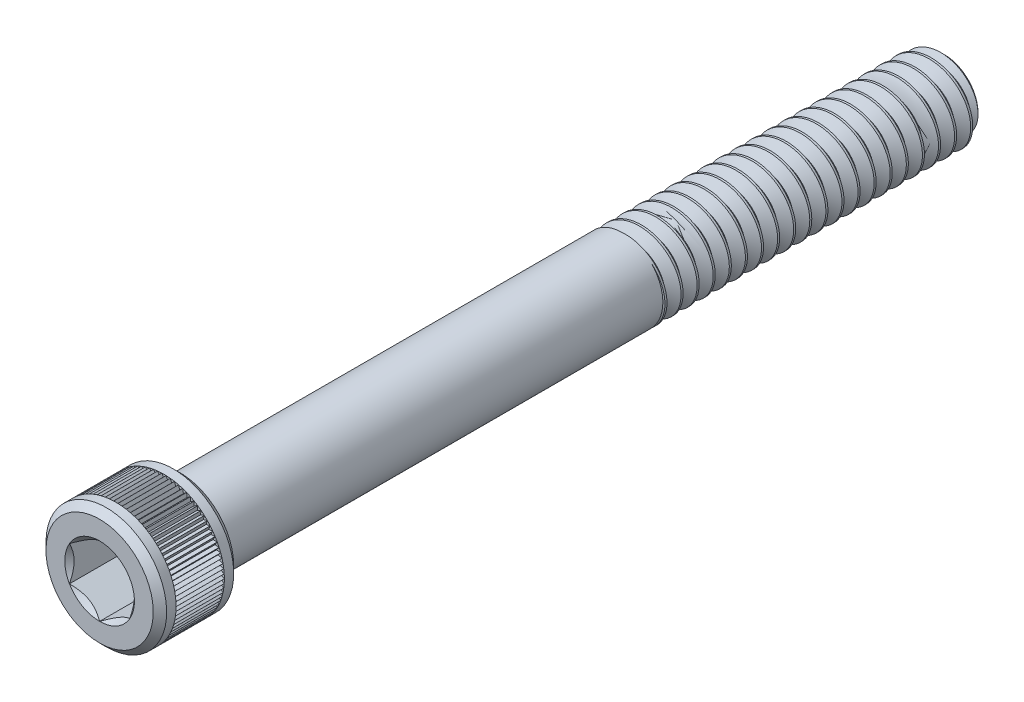
SolidWorks part; units mm, degrees
ref_plane "Front Plane" through (0, 0, 0) normal (0, 0, 1) x (1, 0, 0)
ref_plane "Top Plane" through (0, 0, 0) normal (0, 1, 0) x (1, 0, 0)
ref_plane "Right Plane" through (0, 0, 0) normal (1, 0, 0) x (0, 0, -1)
sketch "Sketch1" plane through (0, 0, 0) normal (1, 0, 0) x (0, 0, -1)
  line L0 (-34.925, 0) -> (25.4, 0) construction
  line L1 (-34.925, 4.7625) -> (-34.925, -4.7625) construction
  line L2 (25.4, 3.175) -> (25.4, -3.175) construction
  line L3 (25.4, 3.175) -> (26.67, 3.175) construction
  line L4 (-34.925, 4.7625) -> (-41.275, 4.7625) construction
  line L5 (-41.275, -2.3812) -> (-41.275, 2.3812) construction
  point P5 (0, 3.175)
  point P6 (22.225, -3.175)
  point P9 (25.4, 0)
  point P14 (-41.275, 0)
  point P15 (-22.225, 0)
  point P16 (-12.7, 0)
  point P17 (-40.005, 4.7625)
  point P18 (-36.195, 4.7625)
  dimension "Pitch" = 1.27
  dimension "Thread OD" = 6.35
  dimension "Minimum Thread Length" = 25.4
  dimension "Head Diameter" = 9.525
  dimension "Head Height" = 6.35
  dimension "Length" = 60.325
  dimension "Drive Size" = 4.7625
  dimension "D1" = 3.175
  dimension "D2" = 12.7
  dimension "D3" = 12.7
  dimension "D4" = 1.27
  dimension "D5" = 1.27
sketch "Sketch12" plane through (0, 0, 0) normal (0, 0, 1) x (1, 0, 0)
  line L0 (-0.1663, 4.7625) -> (0.1663, 4.7625)
  line L1 (0.1663, 4.7625) -> (0, 4.4744)
  line L2 (0, 4.4744) -> (-0.1663, 4.7625)
  line L3 (-0.1663, 4.7625) -> (0, 0) construction
  line L4 (0, 0) -> (0.1663, 4.7625) construction
  dimension "Knurl Angle" = 4
sketch "Sketch2" plane through (0, 0, 0) normal (1, 0, 0) x (0, 0, -1)
  line L0 (-41.275, 0) -> (25.4, 0)
  line L1 (-40.7458, 4.7625) -> (-35.4542, 4.7625)
  line L2 (-41.275, 4.2333) -> (-41.275, 0)
  line L4 (-34.925, 4.2333) -> (-34.925, 3.175)
  line L5 (25.4, 0) -> (25.4, 2.6458)
  line L6 (24.8708, 3.175) -> (-34.925, 3.175)
  line L7 (-34.925, 4.2333) -> (-35.4542, 4.7625)
  line L8 (-41.275, 4.2333) -> (-40.7458, 4.7625)
  line L9 (24.8708, 3.175) -> (25.4, 2.6458)
  line L10 (-34.925, 4.7625) -> (-41.275, 4.7625) construction
  line L11 (-34.925, 4.7625) -> (-34.925, -4.7625) construction
  point P0 (-38.1, 4.7625)
  dimension "D1" = 45
  dimension "D2" = 0.5292
revolve "Revolve1" add sketch "Sketch2" angle 360 about L0
sketch "Sketch3" plane through (0, 0, 41.275) normal (0, 0, 1) x (1, 0, 0)
  line L0 (-2.3813, 0) -> (2.3812, 0) construction
  line L1 (0, 2.7496) -> (-2.3813, 1.3748)
  line L2 (-2.3813, 1.3748) -> (-2.3813, -1.3748)
  line L3 (-2.3813, -1.3748) -> (0, -2.7496)
  line L4 (0, -2.7496) -> (2.3813, -1.3748)
  line L5 (2.3813, -1.3748) -> (2.3813, 1.3748)
  line L6 (2.3813, 1.3748) -> (0, 2.7496)
  line L7 (0, -2.3812) -> (0, 2.3812) construction
  circle A0 centre (0, 0) radius 2.3813 construction
extrude "Cut-Extrude1" cut sketch "Sketch3" against normal blind 4.7625
sketch "Sketch4" plane through (0, 0, 41.275) normal (0, 0, 1) x (1, 0, 0)
  circle A0 centre (0, 0) radius 2.7496
extrude "Cut-Extrude2" cut sketch "Sketch4" against normal through all draft 45
split "Split1" trim tools "Front Plane" bodies to split 106 resulting bodies 107 108
sketch "Sketch6" plane through (0, 0, -25.4) normal (0, 0, -1) x (-1, 0, 0)
  line L0 (0, -2.3812) -> (0, 2.3812) construction
  circle A0 centre (0, 0) radius 3.175
sketch "Sketch7" plane through (0, 0, 0) normal (1, 0, 0) x (0, 0, -1)
  line L0 (25.4, 3.175) -> (26.5113, 3.175) construction
  line L1 (26.5113, 3.175) -> (25.9556, 2.2126) construction
  line L2 (25.9556, 2.2126) -> (25.4, 3.175) construction
  line L3 (25.4, 3.175) -> (25.3206, 3.3125) construction
  line L4 (25.3206, 3.3125) -> (26.5906, 3.3125) construction
  line L5 (26.5906, 3.3125) -> (26.5113, 3.175) construction
  line L6 (25.8763, 2.3501) -> (26.035, 2.3501) construction
  line L7 (25.9556, 3.175) -> (25.9556, 3.3125) construction
  line L8 (25.9556, 2.3501) -> (25.9556, 2.2126) construction
  line L9 (25.4, 3.175) -> (26.67, 3.175) construction
  dimension "D1" = 0.1588
curve "Helix/Spiral1" pitch 1.27 height 27.94 turns 22
sketch "Sketch8" plane through (0, 0, 0) normal (1, 0, 0) x (0, 0, -1)
  line L0 (25.3603, 3.2437) -> (26.5509, 3.2437)
  line L1 (25.4, 3.175) -> (25.3206, 3.3125) construction
  line L2 (26.5906, 3.3125) -> (26.5113, 3.175) construction
  line L3 (26.5509, 3.2437) -> (26.035, 2.3501)
  line L4 (26.035, 2.3501) -> (25.8763, 2.3501)
  line L5 (25.8763, 2.3501) -> (25.3603, 3.2437)
sweep "Cut-Sweep1" cut profiles "Sketch8" path "Helix/Spiral1" align with end faces yes
combine bodies "Combine1" operation type add bodies to combine 109 107
sketch "Sketch14" plane through (0, 0, 0) normal (0, 0, 1) x (1, 0, 0)
  line L0 (0.1663, 4.7625) -> (0, 4.4744) construction
  line L1 (0, 4.4744) -> (-0.1663, 4.7625) construction
  line L2 (-0.1663, 4.7625) -> (0.1663, 4.7625) construction
  line L3 (0.1663, 4.7625) -> (0, 4.4744)
  line L4 (0, 4.4744) -> (-0.1663, 4.7625)
  line L5 (-0.1663, 4.7625) -> (0.1663, 4.7625)
extrude "Cut-Extrude3" cut sketch "Sketch14" against normal up to vertex (-36.195 mm away) from vertex at 40.005 starting at point (0, 4.7625, 40.005)
pattern_circular "CirPattern1" count 90 over 360 about axis through (0, 0, 0) along (0, 0, 1) of "Cut-Extrude3"
equation "\"D1@Cut-Extrude1\"=\"Head Height@Sketch1\"*.75"
equation "\"D2@Sketch2\"=( \"Head Diameter@Sketch1\" - \"Thread OD@Sketch1\" )  / 6"
equation "\"D3@Helix/Spiral1\" = \"Minimum Thread Length@Sketch1\" +  ( 2 * \"Pitch@Sketch1\" ) "
equation "\"D1@Sketch7\"=\"Pitch@Sketch1\"/8"
equation "\"D4@Helix/Spiral1\"=\"Pitch@Sketch1\""
equation "\"D1@Sketch1\"=\"Pitch@Sketch1\"*2.5"
equation "\"D2@Sketch1\"=\"Thread OD@Sketch1\"*2"
equation "\"D3@Sketch1\"=\"D2@Sketch1\""
equation "\"D4@Sketch1\"=\"Head Height@Sketch1\"*.2"
equation "\"D1@CirPattern1\"=360/\"Knurl Angle@Sketch12\""
equation "\"D5@Sketch1\"=\"Head Height@Sketch1\"*.2"
